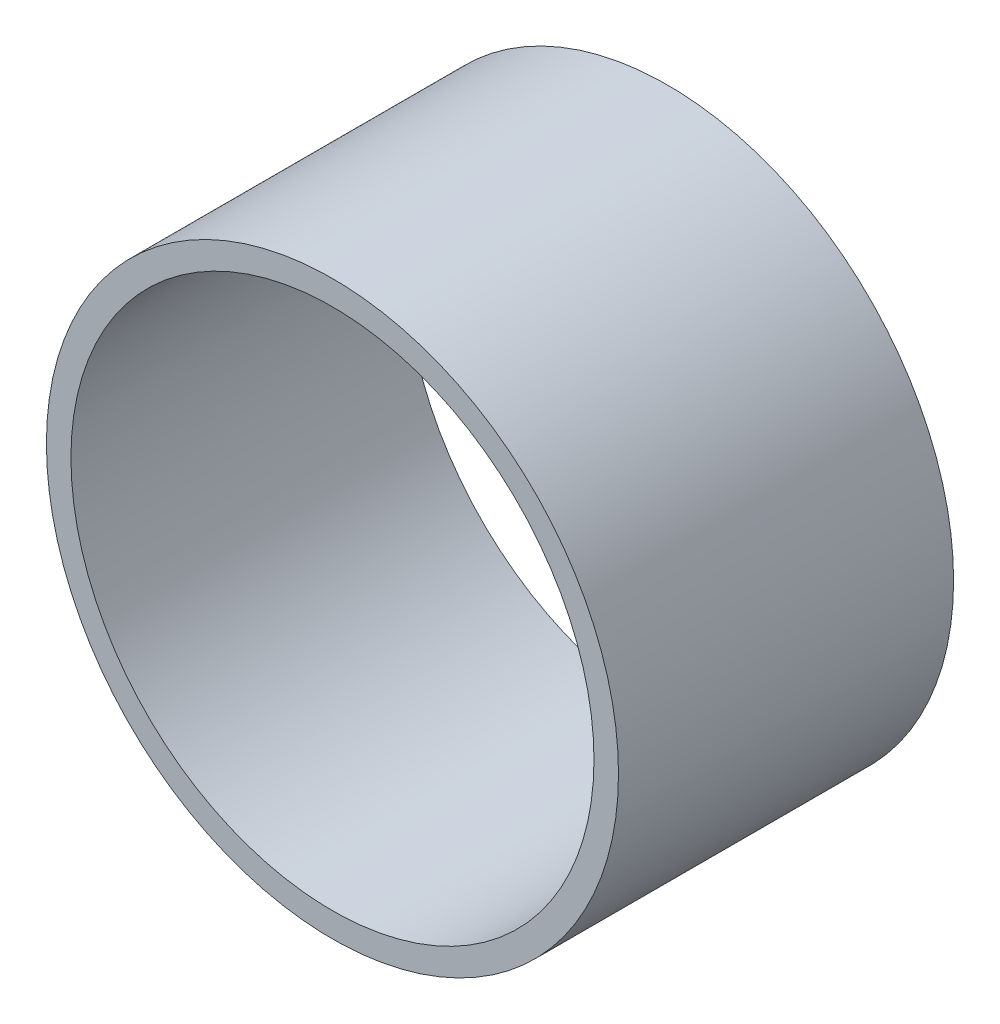
SolidWorks part; units mm, degrees
material "Acrylic (Medium-high impact)"
ref_plane "Front Plane" through (0, 0, 0) normal (0, 0, 1) x (1, 0, 0)
ref_plane "Top Plane" through (0, 0, 0) normal (0, 1, 0) x (1, 0, 0)
ref_plane "Right Plane" through (0, 0, 0) normal (1, 0, 0) x (0, 0, -1)
sketch "Sketch1" plane through (0, 0, 0) normal (0, 0, 1) x (1, 0, 0)
  circle A0 centre (0, 0) radius 35
  circle A1 centre (0, 0) radius 32
  dimension "D1" = 64
  dimension "D2" = 70
extrude "Boss-Extrude1" add sketch "Sketch1" along normal blind 20.5 and the other way blind 20.5
